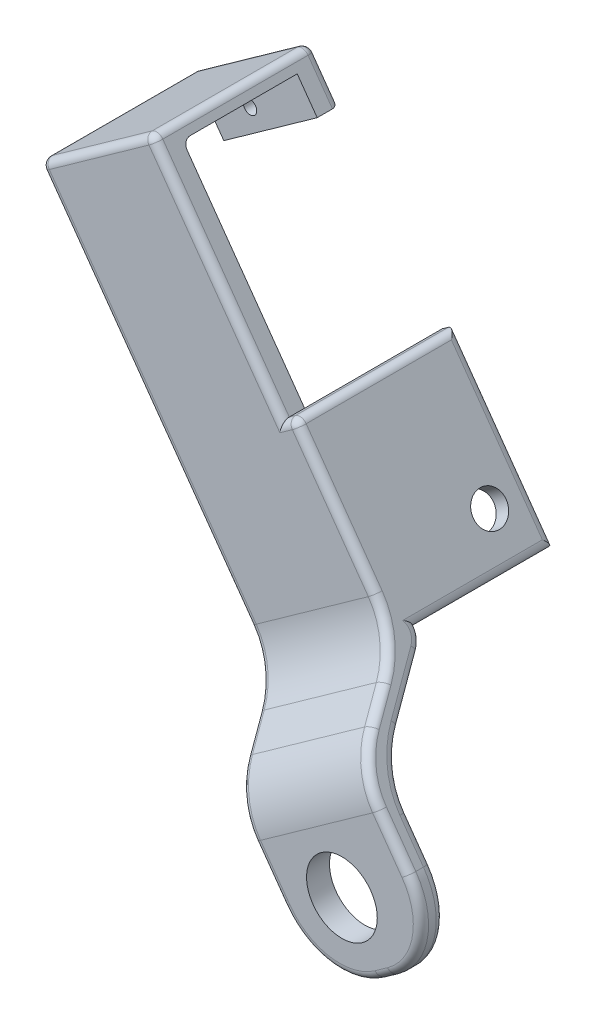
SolidWorks part; units mm, degrees
ref_plane "Front Plane" through (0, 0, 0) normal (0, 0, 1) x (1, 0, 0)
ref_plane "Top Plane" through (0, 0, 0) normal (0, 1, 0) x (1, 0, 0)
ref_plane "Right Plane" through (0, 0, 0) normal (1, 0, 0) x (0, 0, -1)
sketch "Sketch1" plane through (7.3286, 5.2241, 0) normal (0.8143, 0.5805, 0) x (0, 0, -1)
  line L0 (-55, -39.5) -> (-55, 10.5)
  line L1 (-55, -54.0119) -> (-55, -23) construction
  line L3 (-37, 10.5) -> (-37, 12.5)
  line L4 (-37, 12.5) -> (-58, 12.5)
  line L5 (-58, 12.5) -> (-58, -39.5)
  line L6 (-58, -39.5) -> (-55, -39.5)
  line L7 (-55, 10.5) -> (-40, 10.5)
  line L8 (-37, 4.5) -> (-37, -18.5) construction
  line L10 (-54, -39.5) -> (-50.75, -39.5) construction
  line L11 (-40, 10.5) -> (-40, 6)
  line L12 (-40, 6) -> (-37, 6)
  line L13 (-40, 7.625) -> (-40, 9.375) construction
  line L14 (-37, 6) -> (-37, 10.5)
  line L15 (-37, 10.5) -> (-40, 10.5) construction
  line L16 (-40, 6) -> (-51, 6) construction
  dimension "D1" = 2
  dimension "D2" = 3
extrude "Boss-Extrude1" add sketch "Sketch1" against normal up to surface (18 mm away)
sketch "Sketch2" plane through (7.3286, 5.2241, 0) normal (0.8143, 0.5805, 0) x (0, 0, -1)
  line L0 (-58, 12.5) -> (-58, -39.5) construction
  line L1 (-58, -17) -> (-37, -17)
  line L2 (-58, -17) -> (-58, -39.5)
  line L3 (-58, -39.5) -> (-37, -39.5)
  line L4 (-37, -17) -> (-37, -39.5)
  line L5 (-54, -17) -> (-38, -17) construction
  line L6 (-58, -39.5) -> (-55, -39.5) construction
  line L7 (-37, -20.375) -> (-37, -18.625) construction
extrude "Boss-Extrude2" add sketch "Sketch2" along normal blind 2
sketch "Sketch3" plane through (8.9572, 6.385, 0) normal (0.8143, 0.5805, 0) x (0, 0, -1)
  line L0 (-58, -39.5) -> (-67.75, -48.5)
  line L1 (-67.75, -48.5) -> (-67.75, -68.5)
  line L2 (-67.75, -68.5) -> (-64.75, -68.5)
  line L3 (-64.75, -68.5) -> (-64.75, -49.8135)
  line L4 (-64.75, -49.8135) -> (-53.577, -39.5)
  line L5 (-58, -39.5) -> (-37, -39.5) construction
  line L6 (-58, -39.5) -> (-37, -39.5) construction
  line L7 (-58, -39.5) -> (-53.577, -39.5)
  line L8 (-55, -39.5) -> (-55, -40.8135)
  line L9 (-55, -17) -> (-55, 10.5) construction
  line L10 (-58, -17) -> (-58, -39.5) construction
  line L11 (-28.25, -68.5) -> (-29.25, -68.5) construction
  line M8 (-58, -39.5) -> (-37, -39.5)
  dimension "D1" = 3
  dimension "D2" = 20
  dimension "D3" = 3
  dimension "D4" = 9.75
extrude "Boss-Extrude3" add sketch "Sketch3" against normal up to surface (20 mm away) contours L8 L0 L1 L2 L3 L4 M8 up to face at (-5.8049, -7.3616, 47.5)
sketch "Sketch5" plane through (0, 0, 67.75) normal (0, 0, 1) x (1, 0, 0)
  circle A0 centre (34.8275, -48.8574) radius 4.625
  dimension "D1" = 9.25
extrude "Cut-Extrude1" cut sketch "Sketch5" against normal through all and the other way through all
sketch "Sketch8" plane through (-3.4828, 4.8857, 0) normal (0.5805, -0.8143, 0) x (0.8143, 0.5805, 0)
  line L0 (-9, 37) -> (9, 37) construction
  line L1 (-9, 40) -> (-6, 40)
  line L2 (-9, 40) -> (-9, 37)
  line L3 (-9, 37) -> (-6, 37)
  line L4 (-6, 40) -> (-6, 37)
  line L5 (-6, 51) -> (-6, 54) construction
extrude "Cut-Extrude3" cut sketch "Sketch8" against normal up to surface (4.5 mm away) up to face at (-6.0948, 8.55, 47.5)
fillet "Fillet3" radius 10 3 edges at (23.7424, -31.584, 58) (28.9665, -38.9126, 67.75) (29.729, -39.9822, 64.75)
fillet "Fillet2" radius 9 2 edges at (32.4328, -61.003, 66.25) (48.7186, -49.3938, 66.25)
fillet "Fillet4" radius 3 1 edges at (24.5048, -32.6536, 55)
fillet "Fillet1" radius 1 36 edges at (41.9539, -39.904, 64.75) (45.042, -48.7774, 64.75) (33.0492, -57.3264, 64.75) (45.042, -48.7774, 67.75) (33.0492, -57.3264, 67.75) (32.5837, -26.7592, 55.2519) (1.088, -17.0313, 55) (16.2979, -38.3683, 55.2519) (1.9594, 12.7563, 37) (18.0107, -8.0383, 58) (24.0844, -14.836, 58) (25.3551, -16.6186, 37) (0.0729, 15.4027, 47.5) (18.825, -7.4579, 47.5) (8.6346, 3.392, 58) (31.8853, -25.7794, 46) (-7.2557, 10.1786, 37) (-14.5843, 4.9545, 47.5) (-7.2557, 10.1786, 58) (-0.7631, -14.4344, 58) (-2.2613, 5.7564, 37) (18.2116, -41.0529, 62.875) (34.4974, -29.4437, 62.875) (41.5727, -39.3692, 67.75) (34.6565, -29.6669, 58.749) (37.3228, -33.4073, 66.9105) (25.2869, -50.9784, 67.75) (18.3707, -41.2761, 58.749) (21.037, -45.0165, 66.9105) (31.6719, -25.4801, 58.8395) (15.3861, -37.0893, 58.8395) (38.0852, -34.4769, 63.9105) (21.7994, -46.0861, 63.9105) (40.5757, -55.1984, 67.75) (40.5757, -55.1984, 64.75) (25.6681, -51.5132, 64.75)
fillet "Fillet5" radius 1 2 edges at (-13.1849, 3.4959, 55.2929) (-5.6877, 8.8403, 55)
sketch "Sketch7" plane through (0, 0, 55) normal (0, 0, -1) x (-1, 0, 0)
  line L0 (-30.2567, -26.9403) -> (-16.4138, -36.8081) construction
  line L1 (-25.371, -30.4231) -> (-22.1138, -32.7449)
  line L2 (-25.371, -30.4231) -> (-22.4687, -26.3516)
  line L3 (-22.4687, -26.3516) -> (-19.2115, -28.6735)
  line L4 (-22.1138, -32.7449) -> (-19.2115, -28.6735)
  line L6 (-18.8628, -28.615) -> (-21.3298, -32.0757) construction
  dimension "D1" = 4
  dimension "D2" = 5
  dimension "D3" = 0.25
extrude "Boss-Extrude4" add sketch "Sketch7" along normal blind 4
sketch "Sketch9" plane through (0, 0, 37) normal (0, 0, -1) x (-1, 0, 0)
  circle A0 centre (4.9339, 6.9215) radius 0.875 construction
  circle A1 centre (4.9339, 6.9215) radius 0.875
extrude "Cut-Extrude4" cut sketch "Sketch9" against normal up to surface (3 mm away) up to face at (-3.5673, 7.5886, 40)
hole_wizard "M4 Clearance Hole1" positions "Sketch10" profile "Sketch11" hole size "M4" standard "ANSI Metric"
sketch "Sketch10" plane through (8.9572, 6.385, 0) normal (0.8143, 0.5805, 0) x (0, 0, -1)
  line L0 (-37, -17) -> (-37, -39.5) construction
  line L1 (-37, -39.5) -> (-55, -39.5) construction
  point P0 (-42, -33.5)
  dimension "D1" = 5
  dimension "D2" = 6
sketch "Sketch11" plane through (28.4025, -20.8937, 42) normal (0, 0, 1) x (-0.5805, 0.8143, 0)
  line L0 (0, 0) -> (0, 6.2919)
  line L1 (0, 6.2919) -> (2.15, 5)
  line L2 (2.15, 5) -> (2.15, 0)
  line L5 (2.15, 0) -> (0, 0)
  line L10 (0, 6.2919) -> (-2.15, 5) construction
  line L11 (0, -6.35) -> (0, 107.95) construction
  dimension "Hole Dia." = 4.3
  dimension "Hole Depth" = 5
  dimension "Drill Angle" = 118
